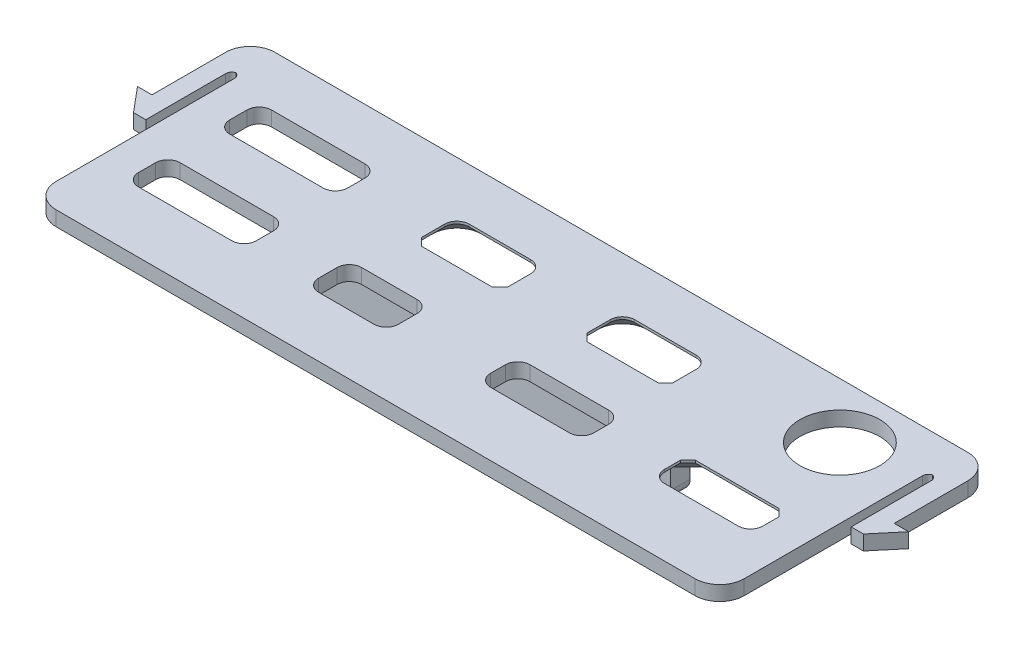
SolidWorks part; units mm, degrees
ref_plane "前视基准面" through (0, 0, 0) normal (0, 0, 1) x (1, 0, 0)
ref_plane "上视基准面" through (0, 0, 0) normal (0, 1, 0) x (1, 0, 0)
ref_plane "右视基准面" through (0, 0, 0) normal (1, 0, 0) x (0, 0, -1)
sketch "草图1" plane through (0, 0, 0) normal (0, 1, 0) x (1, 0, 0)
  line L1 (-30, 10) -> (30, 10)
  line L2 (-30, 10) -> (-30, -10)
  line L3 (-30, -10) -> (30, -10)
  line L4 (30, 10) -> (30, -10)
  line L5 (-30, 10) -> (30, -10) construction
  line L6 (-30, -10) -> (30, 10) construction
  point P0 (0, 0)
  dimension "D1" = 60
  dimension "D2" = 20
extrude "凸台-拉伸1" add sketch "草图1" along normal blind 1.2
sketch "草图4" plane through (0, 1.2, 0) normal (0, 1, 0) x (1, 0, 0)
  line L0 (-30, 10) -> (-30, -10) construction
  line L1 (-25.2717, 5.8) -> (-15.6717, 5.8)
  line L2 (-25.2717, 5.8) -> (-25.2717, 2.4)
  line L3 (-25.2717, 2.4) -> (-15.6717, 2.4)
  line L4 (-15.6717, 5.8) -> (-15.6717, 2.4)
  line L5 (-9.1829, 5.8) -> (-2.1829, 5.8)
  line L6 (-9.1829, 5.8) -> (-9.1829, 2.3)
  line L7 (-9.1829, 2.3) -> (-2.1829, 2.3)
  line L8 (-2.1829, 5.8) -> (-2.1829, 2.3)
  line L9 (4.2885, 5.8) -> (11.2885, 5.8)
  line L10 (4.2885, 5.8) -> (4.2885, 2.3)
  line L11 (4.2885, 2.3) -> (11.2885, 2.3)
  line L12 (11.2885, 5.8) -> (11.2885, 2.3)
  line L13 (17.05, -1.6348) -> (25.05, -1.6348)
  line L14 (17.05, -1.6348) -> (17.05, -4.5348)
  line L15 (17.05, -4.5348) -> (25.05, -4.5348)
  line L16 (25.05, -1.6348) -> (25.05, -4.5348)
  line L17 (3.2, -1.6348) -> (11.6, -1.6348)
  line L18 (3.2, -1.6348) -> (3.2, -4.8348)
  line L19 (3.2, -4.8348) -> (11.6, -4.8348)
  line L20 (11.6, -1.6348) -> (11.6, -4.8348)
  line L21 (-10.5, -1.6348) -> (-4, -1.6348)
  line L22 (-10.5, -1.6348) -> (-10.5, -5.1348)
  line L23 (-10.5, -5.1348) -> (-4, -5.1348)
  line L24 (-4, -1.6348) -> (-4, -5.1348)
  line L25 (-25.2717, -1.6348) -> (-15.6717, -1.6348)
  line L26 (-25.2717, -1.6348) -> (-25.2717, -5.0348)
  line L27 (-25.2717, -5.0348) -> (-15.6717, -5.0348)
  line L28 (-15.6717, -1.6348) -> (-15.6717, -5.0348)
  line L29 (30, 10) -> (-30, 10) construction
  line L30 (-30, -10) -> (30, -10) construction
  line L31 (30, -10) -> (30, 10) construction
  circle A0 centre (22.2985, 5.4832) radius 3.25
  dimension "D21" = 6.5
  dimension "D1" = 3.5
  dimension "D2" = 6.5
  dimension "D3" = 8.4
  dimension "D4" = 3.2
  dimension "D5" = 9.6
  dimension "D6" = 3.4
  dimension "D7" = 7
  dimension "D8" = 8
  dimension "D9" = 2.9
  dimension "D10" = 4.7283
  dimension "D11" = 7.6
  dimension "D12" = 4.9652
  dimension "D13" = 19.5
  dimension "D14" = 33.2
  dimension "D15" = 4.95
  dimension "D16" = 7
  dimension "D17" = 20.8171
  dimension "D18" = 34.2885
  dimension "D19" = 7.7015
  dimension "D20" = 4.5168
  dimension "D22" = 3.5
extrude "切除-拉伸1" cut sketch "草图4" against normal up to next
fillet "圆角2" radius 1 22 edges at (-25.2717, 0.6, -2.4) (-25.2717, 0.6, -5.8) (-15.6717, 0.6, -2.4) (-15.6717, 0.6, -5.8) (-2.1829, 0.6, -5.8) (-9.1829, 0.6, -5.8) (4.2885, 0.6, -5.8) (11.2885, 0.6, -5.8) (25.05, 0.6, 4.5348) (17.05, 0.6, 4.5348) (11.6, 0.6, 4.8348) (11.6, 0.6, 1.6348) (3.2, 0.6, 1.6348) (3.2, 0.6, 4.8348) (-4, 0.6, 5.1348) (-4, 0.6, 1.6348) (-10.5, 0.6, 1.6348) (-10.5, 0.6, 5.1348) (-15.6717, 0.6, 5.0348) (-15.6717, 0.6, 1.6348) (-25.2717, 0.6, 1.6348) (-25.2717, 0.6, 5.0348)
chamfer "倒角1" distance 0.6 angle 45 6 edges at (-9.1829, 0.6, -2.3) (-2.1829, 0.6, -2.3) (4.2885, 0.6, -2.3) (11.2885, 0.6, -2.3) (17.05, 0.6, 1.6348) (25.05, 0.6, 1.6348)
sketch "草图5" plane through (0, 0, 0) normal (0, -1, 0) x (1, 0, 0)
  line L0 (-30, -10) -> (-30, 10) construction
  line L1 (-13.9089, -4.8832) -> (-12.4089, -4.8832)
  line L2 (-13.9089, -4.8832) -> (-13.9089, 3.1168)
  line L3 (-13.9089, 3.1168) -> (-12.4089, 3.1168)
  line L4 (-12.4089, -4.8832) -> (-12.4089, 3.1168)
  line L5 (13.0911, -4.8832) -> (14.5911, -4.8832)
  line L6 (13.0911, -4.8832) -> (13.0911, 3.1168)
  line L7 (13.0911, 3.1168) -> (14.5911, 3.1168)
  line L8 (14.5911, -4.8832) -> (14.5911, 3.1168)
  line L9 (30, -10) -> (-30, -10) construction
  line L10 (30, 10) -> (30, -10) construction
  dimension "D1" = 1.5
  dimension "D2" = 8
  dimension "D3" = 1.5
  dimension "D4" = 8
  dimension "D5" = 16.0911
  dimension "D6" = 5.1168
  dimension "D7" = 5.1168
  dimension "D8" = 15.4089
extrude "凸台-拉伸2" add sketch "草图5" along normal blind 1.2
sketch "草图6" plane through (0, 0, 0) normal (0, -1, 0) x (1, 0, 0)
  line L0 (-13.9089, 3.1168) -> (-13.9089, -4.8832) construction
  line L1 (-13.9089, 0.6) -> (14.5911, 0.6)
  line L2 (-13.9089, 0.6) -> (-13.9089, -1)
  line L3 (-13.9089, -1) -> (14.5911, -1)
  line L4 (14.5911, 0.6) -> (14.5911, -1)
  line L5 (30, -10) -> (-30, -10) construction
  dimension "D1" = 1.6
  dimension "D2" = 9
extrude "凸台-拉伸3" add sketch "草图6" along normal blind 4
fillet "圆角3" radius 1 2 edges at (14.5911, -4, -0.2) (-13.9089, -4, -0.2)
chamfer "倒角2" distance 1 angle 45 4 edges at (13.8411, -1.2, -4.8832) (-13.1589, -1.2, -4.8832) (13.8411, -1.2, 3.1168) (-13.1589, -1.2, 3.1168)
chamfer "倒角4" distance 1 angle 45 24 edges at (11.2885, 0, -3.85) (10.9956, 0, -5.5071) (7.7885, 0, -5.8) (4.5814, 0, -5.5071) (10.9885, 0, -2.6) (4.2885, 0, -3.85) (4.5885, 0, -2.6) (7.7885, 0, -2.3) (-9.1829, 0, -3.85) (-2.1829, 0, -3.85) (-8.89, 0, -5.5071) (-2.4758, 0, -5.5071) (-5.6829, 0, -5.8) (-2.4829, 0, -2.6) (-8.8829, 0, -2.6) (-5.6829, 0, -2.3) (17.35, 0, 1.9348) (21.05, 0, 1.6348) (24.75, 0, 1.9348) (25.05, 0, 2.8848) (17.05, 0, 2.8848) (24.7571, 0, 4.2419) (17.3429, 0, 4.2419) (21.05, 0, 4.5348)
sketch "草图7" plane through (0, 1.2, 0) normal (0, 1, 0) x (1, 0, 0)
  line L0 (30, -10) -> (30, 10) construction
  line L1 (30, 10) -> (28, 10)
  line L2 (30, 10) -> (30, -10)
  line L3 (30, -10) -> (28, -10)
  line L4 (28, 10) -> (28, -10)
  line L5 (-30, -10) -> (30, -10) construction
  line L6 (30, 10) -> (-30, 10) construction
  line L7 (-30, 10) -> (-28, 10)
  line L8 (-30, 10) -> (-30, -10)
  line L9 (-30, -10) -> (-28, -10)
  line L10 (-28, 10) -> (-28, -10)
  line L11 (-30, 10) -> (-30, -10) construction
  dimension "D1" = 2
  dimension "D2" = 2
extrude "切除-拉伸2" cut sketch "草图7" against normal blind 5
sketch "草图11" plane through (0, 1.2, 0) normal (0, 1, 0) x (1, 0, 0)
  line L0 (28, 10) -> (30.2, 10)
  line L1 (28, 10) -> (-28, 10) construction
  line L2 (28, 10) -> (28, -10) construction
  line L3 (30.2, 10) -> (30.2, 2)
  line L4 (30.2, 2) -> (31.7, 2)
  line L5 (31.7, 2) -> (31.7, 0)
  line L6 (31.7, 0) -> (28.7, 0)
  line L7 (28.7, 0) -> (28.7, 7)
  line L8 (28.7, 7) -> (28, 7)
  line L9 (28, 10) -> (28, -10) construction
  line L10 (28, 7) -> (28, 10)
  line L11 (-28, 10) -> (-30.2, 10)
  line L12 (-30.2, 10) -> (-30.2, 2)
  line L13 (-30.2, 2) -> (-31.7, 2)
  line L14 (-31.7, 2) -> (-31.7, 0)
  line L15 (-31.7, 0) -> (-28.7, 0)
  line L16 (-28.7, 0) -> (-28.7, 7)
  line L17 (-28.7, 7) -> (-28, 7)
  line L18 (-28, -10) -> (-28, 10) construction
  line L19 (-28, 7) -> (-28, 10)
  point P24 (0, 0)
  dimension "D1" = 3
  dimension "D2" = 2
  dimension "D3" = 7
  dimension "D4" = 2.2
  dimension "D5" = 3
  dimension "D6" = 1.5
  dimension "D7" = 2.2
  dimension "D8" = 3
  dimension "D9" = 1.5
  dimension "D10" = 7
  dimension "D11" = 2
  dimension "D12" = 3
extrude "凸台-拉伸5" add sketch "草图11" against normal up to surface (1.2 mm away) up to face at (21.05, 0, 2.9848)
fillet "圆角5" radius 2 4 edges at (30.2, 0.6, -10) (-30.2, 0.6, -10) (28, 0.6, 10) (-28, 0.6, 10)
fillet "圆角6" radius 0.5 4 edges at (28, 0.6, -7) (28.7, 0.6, -7) (-28, 0.6, -7) (-28.7, 0.6, -7)
chamfer "倒角5" distance 2 angle 50 1 edges at (31.7, 0.6, 0) first distance on face at (30.2, 0.6, 0)
chamfer "倒角6" distance 2 angle 50 1 edges at (-31.7, 0.6, 0) first distance on face at (-30.2, 0.6, 0)
